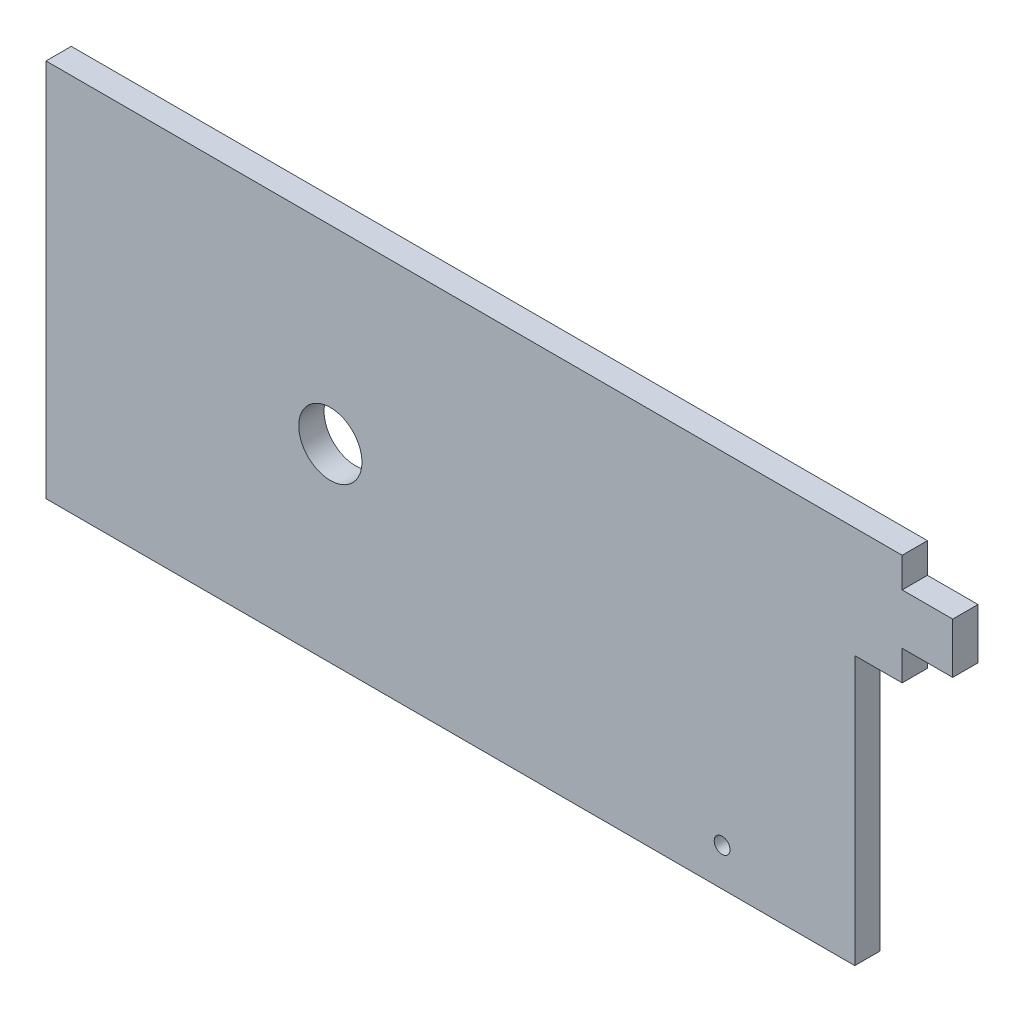
SolidWorks part; units mm, degrees
ref_plane "Front Plane" through (0, 0, 0) normal (0, 0, 1) x (1, 0, 0)
ref_plane "Top Plane" through (0, 0, 0) normal (0, 1, 0) x (1, 0, 0)
ref_plane "Right Plane" through (0, 0, 0) normal (1, 0, 0) x (0, 0, -1)
sketch "Sketch1" plane through (0, 0, 0) normal (0, 0, 1) x (1, 0, 0)
  line L0 (47, 30) -> (54.5, 30)
  line L1 (-81, -30) -> (47, -30)
  line L2 (-81, -30) -> (-81, 30)
  line L3 (-81, 30) -> (47, 30)
  line L4 (47, -30) -> (47, 30) construction
  line L6 (54.5, 12.5) -> (47, 12.5)
  line L11 (54.5, 30) -> (54.5, 12.5) construction
  line L12 (54.5, 30) -> (54.5, 25.25)
  line L13 (47, 12.5) -> (47, -30)
  line L14 (54.5, 25.25) -> (62.5, 25.25)
  line L15 (62.5, 25.25) -> (62.5, 17.25)
  line L16 (62.5, 17.25) -> (54.5, 17.25)
  line L17 (54.5, 17.25) -> (54.5, 12.5)
  circle A4 centre (-36, 0) radius 5
  circle A5 centre (26, -24) radius 1.25
  point P12 (-81, 0)
  dimension "D3" = 17.5
  dimension "D4" = 7.5
  dimension "D5" = 10
  dimension "D1" = 128
  dimension "D6" = 45
  dimension "D9" = 2.5
  dimension "D10" = 107
  dimension "D11" = 6
  dimension "D2" = 60
  dimension "D7" = 8
  dimension "D8" = 8
extrude "Boss-Extrude1" add sketch "Sketch1" along normal blind 4
